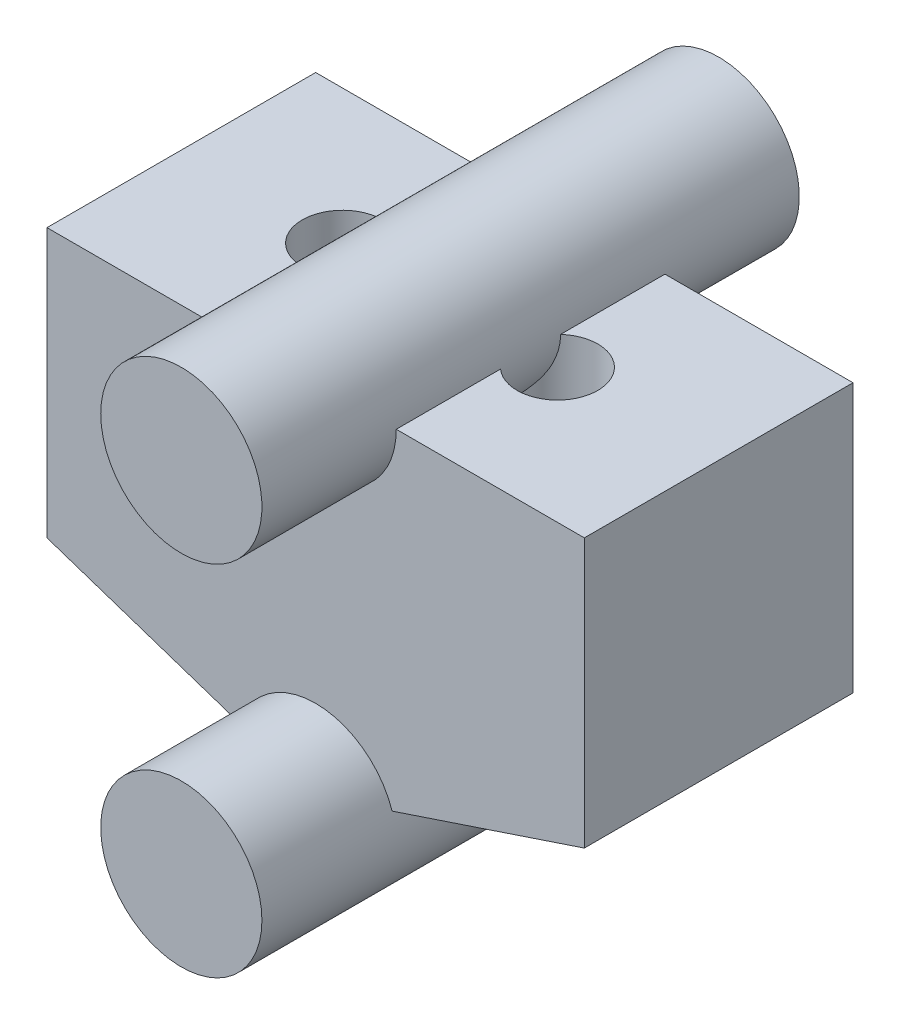
SolidWorks part; units mm, degrees
ref_plane "Front Plane" through (0, 0, 0) normal (0, 0, 1) x (1, 0, 0)
ref_plane "Top Plane" through (0, 0, 0) normal (0, 1, 0) x (1, 0, 0)
ref_plane "Right Plane" through (0, 0, 0) normal (1, 0, 0) x (0, 0, -1)
sketch "Sketch1" plane through (0, 0, 0) normal (0, 0, 1) x (1, 0, 0)
  line L0 (-10, -5) -> (-2.846, -7.3847)
  line L1 (-10, 5) -> (10, 5)
  line L2 (-10, 5) -> (-10, -5)
  line L4 (10, 5) -> (10, -5)
  line L5 (-10, 5) -> (10, -5) construction
  line L6 (-10, -5) -> (10, 5) construction
  line L7 (2.846, -7.3847) -> (10, -5)
  line L8 (-10, -5) -> (0, -8.3333) construction
  circle A0 centre (0, -8.3333) radius 3
  point P0 (0, 0)
  dimension "D4" = 6
  dimension "D1" = 10
  dimension "D2" = 20
  dimension "D3" = 13.3333
extrude "Boss-Extrude1" add sketch "Sketch1" along normal blind 10 contours A0 L7 L4 L1 L2 L0 region at (0, -0.5723, 0)
extrude "Boss-Extrude2" add sketch "Sketch1<3>" along normal blind 15 and the other way blind 5 contours A0 region at (0, -8.3333, 0)
sketch "Sketch1<3>" plane through (0, 0, 0) normal (0, 0, 1) x (1, 0, 0) same geometry as "Sketch1"
sketch "Sketch2" plane through (0, 5, 0) normal (0, 1, 0) x (1, 0, 0)
  line L0 (-10, 0) -> (10, 0) construction
  line L1 (-10, -10) -> (-10, 0) construction
  line L2 (0, -55) -> (0, 55) construction
  circle A0 centre (-4, -5) radius 1.5
  circle A1 centre (4, -5) radius 1.5
  dimension "D1" = 3
  dimension "D2" = 5
  dimension "D3" = 6
extrude "Cut-Extrude1" cut sketch "Sketch2" against normal through all
sketch "Sketch3" plane through (0, 0, 0) normal (0, 0, -1) x (-1, 0, 0)
  line L0 (10, 5) -> (-10, 5) construction
  circle A0 centre (0, 5) radius 3
  dimension "D1" = 6
extrude "Boss-Extrude3" add sketch "Sketch3" along normal blind 5 and the other way blind 15
